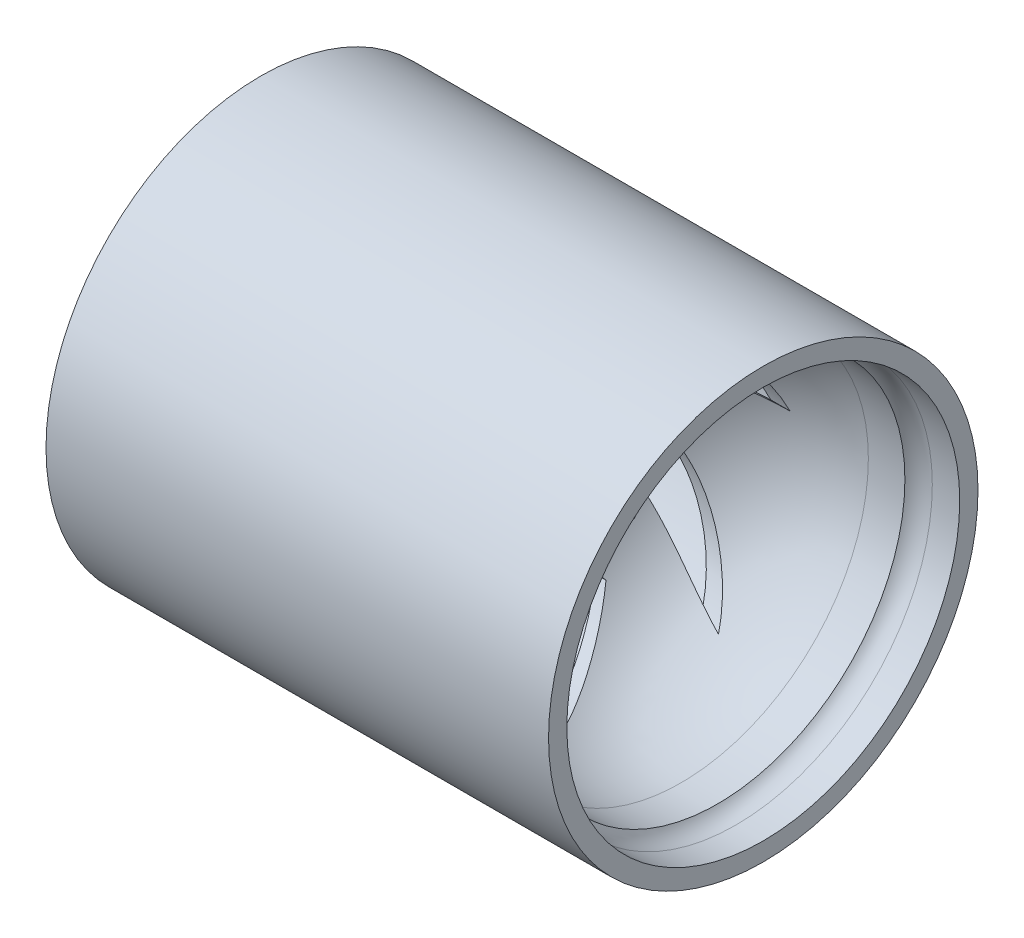
SolidWorks part; units mm, degrees
material "PE High Density"
ref_plane "Front Plane" through (0, 0, 0) normal (0, 0, 1) x (1, 0, 0)
ref_plane "Top Plane" through (0, 0, 0) normal (0, 1, 0) x (1, 0, 0)
ref_plane "Right Plane" through (0, 0, 0) normal (1, 0, 0) x (0, 0, -1)
sketch "Sketch1" plane through (0, 0, 0) normal (0, 0, 1) x (1, 0, 0)
  line L0 (0, 0) -> (60.4764, 0) construction
  line L1 (0, 0) -> (0, 7.375)
  line L2 (0, 7.375) -> (42, 7.375)
  line L3 (42, 7.375) -> (42, 0)
  line L4 (0, 0) -> (42, 0)
  dimension "D1" = 7.375
  dimension "D2" = 42
revolve "Revolve1" add sketch "Sketch1" angle 360 about L0
sketch "Sketch2" plane through (0, 0, 0) normal (0, 0, 1) x (1, 0, 0)
  line L0 (0, 0) -> (58.5117, 0) construction
  line L1 (62, 21.5) -> (62, 23.5)
  line L2 (42, 7.375) -> (0, 7.375) construction
  line L3 (53, 20.5) -> (57, 20.5)
  line L4 (59, 21.5) -> (62, 21.5)
  line L5 (62, 23.5) -> (7, 23.5)
  line L6 (7, 23.5) -> (7, 7.375)
  line L7 (7, 7.375) -> (37, 7.375)
  line L8 (0, 7.375) -> (0, -7.375) construction
  arc A0 (37, 7.375) -> (53, 20.5) centre (53, 4.1851) cw
  arc A1 (57, 20.5) -> (59, 21.5) centre (59, 19) cw
  dimension "D1" = 23.5
  dimension "D2" = 2
  dimension "D3" = 5
  dimension "D4" = 55
  dimension "D5" = 7
  dimension "D6" = 25
  dimension "D7" = 4
  dimension "D8" = 1
  dimension "D9" = 3
revolve "Revolve2" add sketch "Sketch2" angle 360 about L0
sketch "Sketch3" plane through (0, 0, 0) normal (-1, 0, 0) x (0, 0, 1)
  circle A0 centre (0, 0) radius 2
  dimension "D1" = 4
extrude "Cut-Extrude1" cut sketch "Sketch3" against normal through all
sketch "Sketch4" plane through (0, 0, 0) normal (0, 0, 1) x (1, 0, 0)
  line L0 (7, 7.375) -> (36.1997, 7.375)
  line L14 (7, 23.5) -> (7, 7.375) construction
  line L15 (7, 7.375) -> (7, 22.5)
  line L16 (7, 22.5) -> (8, 22.5)
  line L17 (0, 0) -> (70.6316, 0) construction
  line L18 (0, 7.375) -> (0, -7.375) construction
  line L19 (7, 7.375) -> (37, 7.375) construction
  line L20 (8, 8.375) -> (36.1997, 8.375)
  line L21 (8, 22.5) -> (8, 8.375)
  line L22 (59, 22.5) -> (8, 22.5)
  line L23 (53, 21.5) -> (56.5505, 21.5)
  line L24 (8, 8.375) -> (36.1997, 8.375) construction
  line L25 (8, 22.5) -> (8, 8.375) construction
  line L26 (59, 22.5) -> (8, 22.5)
  line L27 (53, 21.5) -> (56.5505, 21.5)
  line L28 (36.1997, 7.375) -> (36.1997, 8.375)
  arc A6 (59, 22.5) -> (56.5505, 21.5) centre (59, 19) ccw
  arc A7 (53, 21.5) -> (36.1997, 8.375) centre (53, 4.1851) ccw
  arc A8 (59, 22.5) -> (56.5505, 21.5) centre (59, 19) ccw
  arc A9 (53, 21.5) -> (36.1997, 8.375) centre (53, 4.1851) ccw
  dimension "D1" = 1
revolve "Cut-Revolve1" cut sketch "Sketch4" angle 360 about L17
sketch "Sketch5" plane through (0, 0, 0) normal (1, 0, 0) x (0, 0, -1)
  line L0 (0, 0) -> (0, 25.4697) construction
  line L1 (-1.0648, 11.1719) -> (0, 8.6033)
  arc A0 (0, 8.6033) -> (-5.7775, 11.1719) centre (-0.9394, 14.2723) cw
  arc A1 (-5.7775, 11.1719) -> (7.8285, 17.2607) centre (4.9995, 5.336) cw
  arc A2 (7.8285, 17.2607) -> (-1.0648, 11.1719) centre (12.9129, 0.2954) ccw
extrude "Cut-Extrude5" cut sketch "Sketch5" along normal blind 160
pattern_circular "CirPattern1" count 6 over 360 about axis through (42, 0, 0) along (-1, 0, 0) of "Cut-Extrude5"
sketch "Sketch6" plane through (0, 0, 0) normal (0, 0, 1) x (1, 0, 0)
  line L0 (42, -7.375) -> (42, 7.375) construction
  line L1 (39, 7.375) -> (39, 9.3087)
  line L2 (39, 9.3087) -> (44.4476, 9.3087)
  line L3 (44.4476, 9.3087) -> (44.4476, 4.375)
  line L4 (44.4476, 4.375) -> (42, 4.375)
  line L5 (42, -7.375) -> (42, 7.375) construction
  line L6 (39, 7.375) -> (-1.7229, 7.375) construction
  line L7 (0, 0) -> (75.2016, 0) construction
  arc A0 (42, 4.375) -> (39, 7.375) centre (39, 4.375) ccw
  dimension "D2" = 3
  dimension "D1" = 7.375
revolve "Cut-Revolve2" cut sketch "Sketch6" angle 360 about L7
sketch "Sketch7" plane through (0, 0, 0) normal (1, 0, 0) x (0, 0, -1)
  line L0 (0, 0) -> (0, 5.8) construction
  circle A0 centre (0, 5.8) radius 0.75
  dimension "D1" = 1.5
  dimension "D2" = 5.8
extrude "Boss-Extrude1" add sketch "Sketch7" along normal blind 42
dome "Dome1" faces to dome 1 distance 0.75 reverse direction no elliptical dome no face at (42, 5.8, -0.75) parameters "D1"=0.75
pattern_circular "CirPattern2" count 9 over 360 about axis through (42, 0, 0) along (-1, 0, 0) of "Dome1", "Boss-Extrude1"
